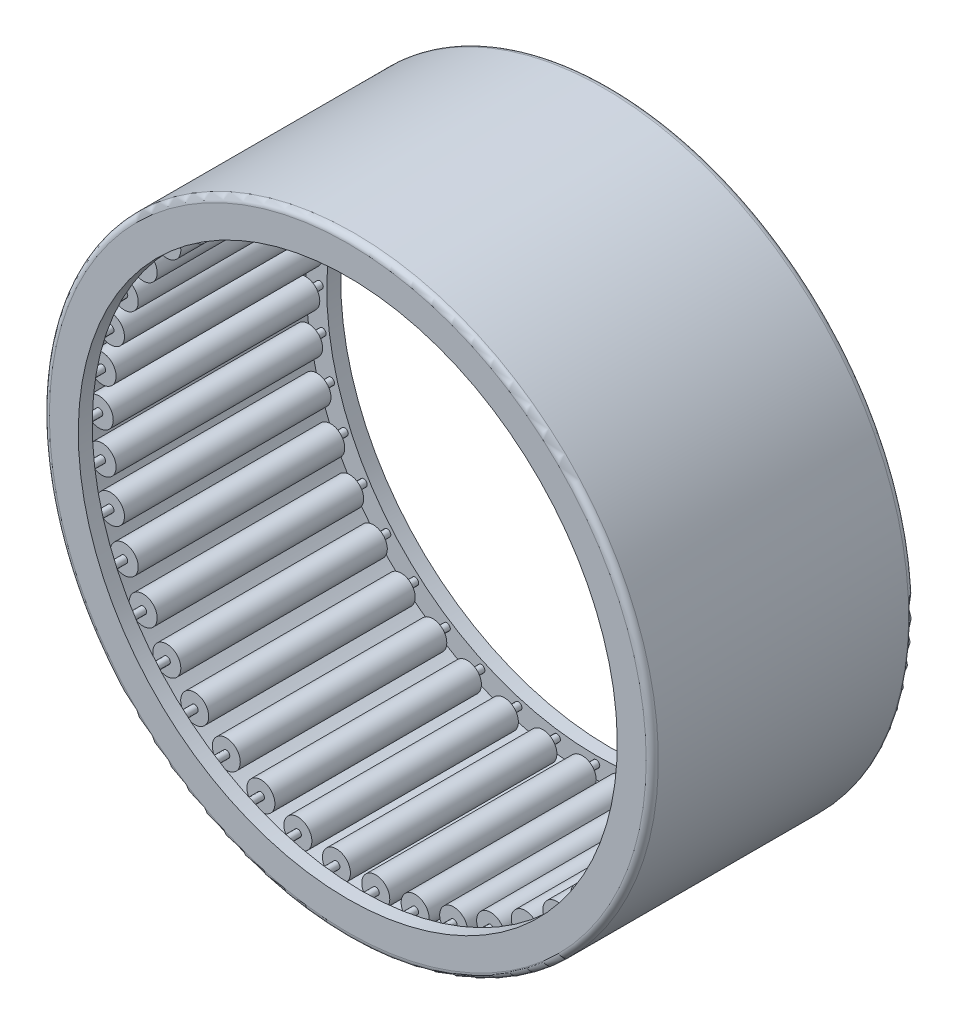
SolidWorks part; units mm, degrees
note: '?' marks a value the reader was unsure of.
material "Alloy Steel"
ref_plane "Front Plane" through (0, 0, 0) normal (0, 0, 1) x (1, 0, 0)
ref_plane "Top Plane" through (0, 0, 0) normal (0, 1, 0) x (1, 0, 0)
ref_plane "Right Plane" through (0, 0, 0) normal (1, 0, 0) x (0, 0, -1)
sketch "Sketch1" plane through (0, 0, 0) normal (1, 0, 0) x (0, 0, -1)
  line L0 (-12.5, 0) -> (12.5, 0) construction
  line L1 (0, 0) -> (0, 29) construction
  line L2 (-12.5, 0) -> (-12.5, 29) construction
  line L3 (-12.5, 29) -> (12.5, 29)
  line L4 (12.5, 29) -> (12.5, 0) construction
  line L5 (12.5, 0) -> (11.1667, 0) construction
  line L6 (11.1667, 0) -> (11.1667, 27.6667) construction
  line L7 (11.1667, 27.6667) -> (-11.1667, 27.6667)
  line L8 (-11.1667, 27.6667) -> (-11.1667, 0) construction
  line L9 (-11.1667, 0) -> (-12.5, 0) construction
  line L10 (-12.5, 29) -> (-12.5, 25.6667)
  line L11 (-12.5, 25.6667) -> (-11.1667, 25.6667)
  line L12 (-11.1667, 25.6667) -> (-11.1667, 27.6667)
  line L13 (11.1667, 29) -> (11.1667, 27.6667) construction
  line L14 (11.1667, 27.6667) -> (11.1667, 25.6667)
  line L15 (11.1667, 25.6667) -> (12.5, 25.6667)
  line L16 (12.5, 25.6667) -> (12.5, 29)
  line L17 (11.1667, 27.6667) -> (11.1667, 26.3333) construction
  line L18 (11.1667, 26.3333) -> (11.1667, 25) construction
  line L19 (11.1667, -27.6667) -> (11.1667, -26.3333) construction
  line L20 (11.1667, -29) -> (11.1667, -27.6667) construction
  line L21 (12.5, -25.6667) -> (12.5, -29) construction
  line L22 (11.1667, -25.6667) -> (12.5, -25.6667) construction
  line L23 (11.1667, -27.6667) -> (11.1667, -25.6667) construction
  line L24 (-11.1667, -25.6667) -> (-11.1667, -27.6667) construction
  line L25 (-12.5, -25.6667) -> (-11.1667, -25.6667) construction
  line L26 (-12.5, -29) -> (-12.5, -25.6667) construction
  line L27 (11.1667, -27.6667) -> (-11.1667, -27.6667) construction
  line L28 (-12.5, -29) -> (12.5, -29) construction
  point P4 (0, 25)
  dimension "C | Width" = 25
  dimension "Fw | ID" = 50
  dimension "D | OD" = 58
sketch "Sketch7" plane through (0, 0, 0) normal (1, 0, 0) x (0, 0, -1)
  line L0 (-12.5, 29) -> (-12.5, 25.6667) construction
  line L1 (-12.5, 25.6667) -> (-11.1667, 25.6667) construction
  line L2 (-11.1667, 25.6667) -> (-11.1667, 27.6667) construction
  line L3 (11.1667, 27.6667) -> (-11.1667, 27.6667) construction
  line L4 (11.1667, 27.6667) -> (11.1667, 25.6667) construction
  line L5 (11.1667, 25.6667) -> (12.5, 25.6667) construction
  line L6 (12.5, 25.6667) -> (12.5, 29) construction
  line L8 (-12.5, 29) -> (12.5, 29) construction
  line L9 (-12.5, 29) -> (-12.5, 25.6667)
  line L10 (-12.5, 25.6667) -> (-11.1667, 25.6667)
  line L13 (-11.1667, 25.6667) -> (-11.1667, 27.6667)
  line L16 (11.1667, 27.6667) -> (-11.1667, 27.6667)
  line L17 (11.1667, 27.6667) -> (11.1667, 25.6667)
  line L18 (11.1667, 25.6667) -> (12.5, 25.6667)
  line L19 (12.5, 25.6667) -> (12.5, 29)
  line L20 (-12.5, 29) -> (12.5, 29)
revolve "Revolve1" add sketch "Sketch7" angle 360 about L0
sketch "Sketch2" plane through (0, 0, 0) normal (1, 0, 0) x (0, 0, -1)
  line L0 (-12.5, 25.6667) -> (-11.1667, 25.6667) construction
  line L1 (-9.8333, 26.3333) -> (9.8333, 26.3333) construction
  line L2 (-9.8333, 26.3333) -> (-9.8333, 27.6667) construction
  line L3 (-9.8333, 27.6667) -> (9.8333, 27.6667)
  line L4 (9.8333, 26.3333) -> (9.8333, 27.6667) construction
  line L5 (11.1667, 25.6667) -> (12.5, 25.6667) construction
  line L6 (-11.1667, 26.3333) -> (-9.8333, 26.3333) construction
  line L7 (9.8333, 26.3333) -> (11.1667, 26.3333) construction
  line L8 (12.5, 29) -> (12.5, 0) construction
  line L9 (-9.8333, 26.6667) -> (-9.8333, 26) construction
  line L10 (-11.1667, 26.3333) -> (-11.1667, 25.6667) construction
  line L11 (-9.8333, 27.6667) -> (-9.8333, 26.6667)
  line L12 (9.8333, 27.6667) -> (9.8333, 26.6667)
  line L13 (9.8333, 26.6667) -> (-9.8333, 26.6667)
  line L14 (0, 27.6667) -> (0, 25) construction
  line L16 (-9.8333, 26) -> (-11.1667, 26) construction
  line L17 (0, 0) -> (12.5, 0) construction
  line L18 (-9.8333, -26) -> (-11.1667, -26) construction
  line L19 (0, -27.6667) -> (0, -25) construction
  line L20 (-11.1667, -26.3333) -> (-11.1667, -25.6667) construction
  line L21 (-9.8333, -26.6667) -> (-9.8333, -26) construction
  line L22 (9.8333, -26.3333) -> (11.1667, -26.3333) construction
  line L23 (-11.1667, -26.3333) -> (-9.8333, -26.3333) construction
  line L24 (9.8333, -26.3333) -> (9.8333, -27.6667) construction
  line L25 (-9.8333, -26.3333) -> (-9.8333, -27.6667) construction
  line L26 (-9.8333, -26.3333) -> (9.8333, -26.3333) construction
  line L27 (9.8333, -26.6667) -> (-9.8333, -26.6667) construction
  line L28 (9.8333, -27.6667) -> (9.8333, -26.6667) construction
  line L29 (-9.8333, -27.6667) -> (-9.8333, -26.6667) construction
  line L30 (-9.8333, -27.6667) -> (9.8333, -27.6667) construction
  line L33 (11.1667, 27.6667) -> (-11.1667, 27.6667) construction
  line L34 (11.1667, 27.6667) -> (11.1667, 25.6667) construction
  line L35 (-11.1667, 25.6667) -> (-11.1667, 27.6667) construction
  line L36 (0, 0) -> (0, 29) construction
  point P16 (0, 26.3333)
revolve "Revolve2" add sketch "Sketch2" angle 360 about L1
sketch "Sketch3" plane through (0, 0, 0) normal (1, 0, 0) x (0, 0, -1)
  line L1 (-11.1667, 26.3333) -> (11.1667, 26.3333)
  line L2 (-11.1667, 26.3333) -> (-11.1667, 26.6667)
  line L3 (-11.1667, 26.6667) -> (11.1667, 26.6667)
  line L4 (11.1667, 26.3333) -> (11.1667, 26.6667)
  line L5 (0, 0) -> (12.5, 0) construction
  line L7 (11.1667, -26.3333) -> (11.1667, -26.6667) construction
  line L8 (-11.1667, -26.6667) -> (11.1667, -26.6667) construction
  line L9 (-11.1667, -26.3333) -> (-11.1667, -26.6667) construction
  line L10 (-11.1667, -26.3333) -> (11.1667, -26.3333) construction
  line L11 (11.1667, 27.6667) -> (11.1667, 25.6667) construction
  line L12 (12.5, 29) -> (12.5, 0) construction
revolve "Revolve3" add sketch "Sketch3" angle 360 about L1
ref_axis "Axis1" through (0, 25.6667, 12.5) along (0, 1, 0)?
pattern_circular "CirPattern1" count 44 every 8.182 about axis through (0, 0, 12.5) along (0, 0, -1)
fillet "Fillet1" radius 0.58 2 edges at (0, -29, -12.5) (0, -29, 12.5)
sketch "Front View" plane through (0, 0, 0) normal (0, 0, 1) x (1, 0, 0)
  circle A0 centre (0, 0) radius 25 construction
  circle A1 centre (0, 0) radius 29 construction
  dimension "ID" = 50
  dimension "OD" = 58
sketch "Right View" plane through (0, 0, 0) normal (1, 0, 0) x (0, 0, -1)
  line L0 (-12.5, 29) -> (12.5, 29) construction
  line L1 (-12.5, 29) -> (12.5, 29) construction
  line L2 (0, 0) -> (0, 29) construction
  point P4 (0, 29)
  dimension "Width" = 25
equation "\"Rollers@CirPattern1\"  = \"OD@Sketch1\"*.75"
equation "\"D1@Fillet1\" = \"D | OD@Sketch1\" * .01"
equation "\"Angle@CirPattern1\"=360 / \"Rollers@CirPattern1\""
equation "\"ID@Front View\" = \"Fw | ID@Sketch1\""
equation "\"OD@Front View\" = \"D | OD@Sketch1\""
equation "\"Width@Right View\" = \"C | Width@Sketch1\""
